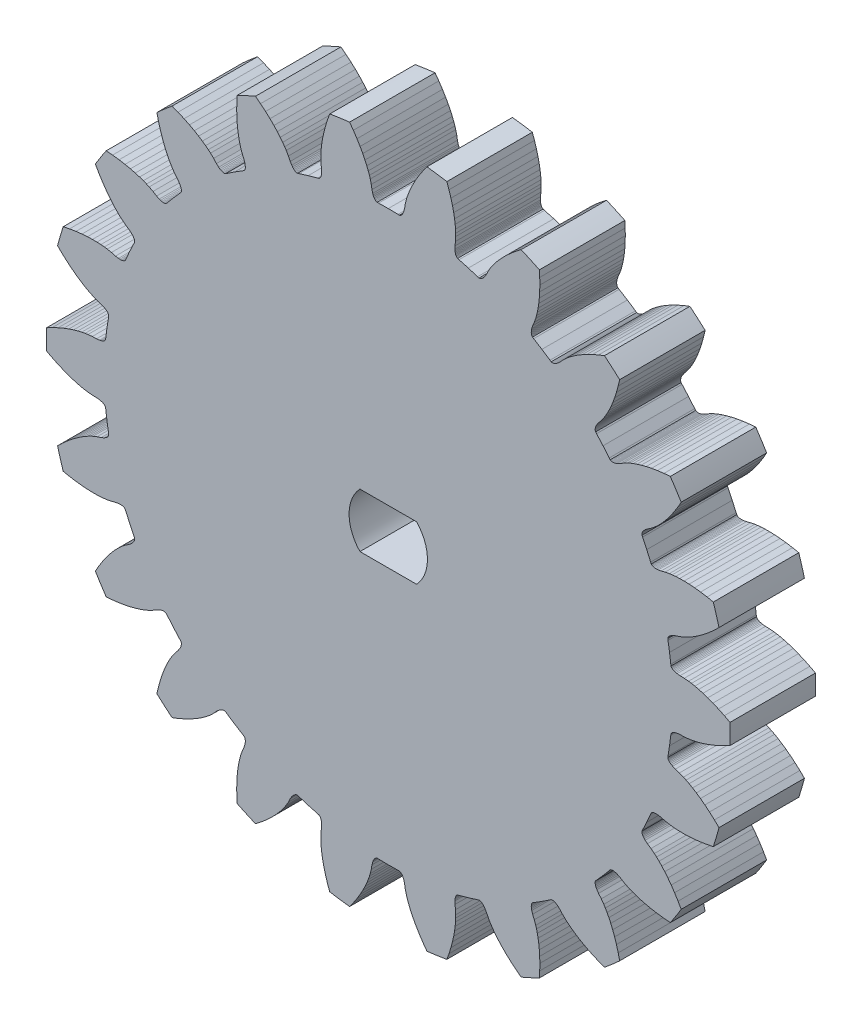
SolidWorks part; units mm, degrees
ref_plane "Front Plane" through (0, 0, 0) normal (0, 0, 1) x (1, 0, 0)
ref_plane "Top Plane" through (0, 0, 0) normal (0, 1, 0) x (1, 0, 0)
ref_plane "Right Plane" through (0, 0, 0) normal (1, 0, 0) x (0, 0, -1)
sketch "Model" plane through (0, 0, 0) normal (0, 0, 1) x (1, 0, 0)
  line L0 (22.8954, 5.7696) -> (22.552, 5.462)
  line L1 (22.552, 5.462) -> (22.2263, 5.1941)
  line L2 (22.2263, 5.1941) -> (21.9171, 4.9606)
  line L3 (21.9171, 4.9606) -> (21.6288, 4.7614)
  line L4 (21.6288, 4.7614) -> (21.3631, 4.5937)
  line L5 (21.3631, 4.5937) -> (21.1212, 4.4548)
  line L6 (21.1212, 4.4548) -> (20.9056, 4.3428)
  line L7 (20.9056, 4.3428) -> (20.7215, 4.2567)
  line L8 (20.7215, 4.2567) -> (20.4399, 4.145)
  line L9 (20.4399, 4.145) -> (20.1563, 4.0551)
  line L10 (20.1563, 4.0551) -> (19.9653, 3.974)
  line L11 (19.9653, 3.974) -> (19.8856, 3.9306)
  line L12 (19.8856, 3.9306) -> (19.8164, 3.8857)
  line L13 (19.8164, 3.8857) -> (19.7579, 3.8399)
  line L14 (19.7579, 3.8399) -> (19.7099, 3.7936)
  line L15 (19.7099, 3.7936) -> (19.6726, 3.7471)
  line L16 (19.6726, 3.7471) -> (19.6458, 3.7009)
  line L17 (19.6458, 3.7009) -> (19.6296, 3.6554)
  line L18 (19.6296, 3.6554) -> (19.6238, 3.6111)
  line L19 (19.6238, 3.6111) -> (19.6389, 3.5098)
  line L20 (19.6389, 3.5098) -> (19.7469, 2.8392)
  line L21 (19.7469, 2.8392) -> (19.8322, 2.1653)
  line L22 (19.8322, 2.1653) -> (19.8463, 2.0638)
  line L23 (19.8463, 2.0638) -> (19.8643, 2.0229)
  line L24 (19.8643, 2.0229) -> (19.8927, 1.9839)
  line L25 (19.8927, 1.9839) -> (19.9314, 1.9471)
  line L26 (19.9314, 1.9471) -> (19.9803, 1.913)
  line L27 (19.9803, 1.913) -> (20.0394, 1.8821)
  line L28 (20.0394, 1.8821) -> (20.1085, 1.8546)
  line L29 (20.1085, 1.8546) -> (20.1874, 1.831)
  line L30 (20.1874, 1.831) -> (20.2762, 1.8118)
  line L31 (20.2762, 1.8118) -> (20.4822, 1.7879)
  line L32 (20.4822, 1.7879) -> (20.7797, 1.7815)
  line L33 (20.7797, 1.7815) -> (21.0814, 1.7537)
  line L34 (21.0814, 1.7537) -> (21.2823, 1.7229)
  line L35 (21.2823, 1.7229) -> (21.5207, 1.6762)
  line L36 (21.5207, 1.6762) -> (21.7919, 1.6111)
  line L37 (21.7919, 1.6111) -> (22.0942, 1.525)
  line L38 (22.0942, 1.525) -> (22.4268, 1.4151)
  line L39 (22.4268, 1.4151) -> (22.7893, 1.2782)
  line L40 (22.7893, 1.2782) -> (23.1773, 1.1129)
  line L41 (23.1773, 1.1129) -> (23.5935, 0.9145)
  line L42 (23.5935, 0.9145) -> (23.9896, 0.7057)
  line L43 (23.9896, -0.7057) -> (23.5935, -0.9145)
  line L44 (23.5935, -0.9145) -> (23.1773, -1.1129)
  line L45 (23.1773, -1.1129) -> (22.7893, -1.2782)
  line L46 (22.7893, -1.2782) -> (22.4268, -1.4151)
  line L47 (22.4268, -1.4151) -> (22.0942, -1.525)
  line L48 (22.0942, -1.525) -> (21.7919, -1.6111)
  line L49 (21.7919, -1.6111) -> (21.5207, -1.6762)
  line L50 (21.5207, -1.6762) -> (21.2823, -1.7229)
  line L51 (21.2823, -1.7229) -> (21.0814, -1.7537)
  line L52 (21.0814, -1.7537) -> (20.7797, -1.7815)
  line L53 (20.7797, -1.7815) -> (20.4822, -1.7879)
  line L54 (20.4822, -1.7879) -> (20.2762, -1.8118)
  line L55 (20.2762, -1.8118) -> (20.1874, -1.831)
  line L56 (20.1874, -1.831) -> (20.1085, -1.8546)
  line L57 (20.1085, -1.8546) -> (20.0394, -1.8821)
  line L58 (20.0394, -1.8821) -> (19.9803, -1.913)
  line L59 (19.9803, -1.913) -> (19.9314, -1.9471)
  line L60 (19.9314, -1.9471) -> (19.8927, -1.9839)
  line L61 (19.8927, -1.9839) -> (19.8643, -2.0229)
  line L62 (19.8643, -2.0229) -> (19.8463, -2.0638)
  line L63 (19.8463, -2.0638) -> (19.8322, -2.1653)
  line L64 (19.8322, -2.1653) -> (19.7469, -2.8392)
  line L65 (19.7469, -2.8392) -> (19.6389, -3.5098)
  line L66 (19.6389, -3.5098) -> (19.6238, -3.6111)
  line L67 (19.6238, -3.6111) -> (19.6296, -3.6554)
  line L68 (19.6296, -3.6554) -> (19.6458, -3.7009)
  line L69 (19.6458, -3.7009) -> (19.6726, -3.7471)
  line L70 (19.6726, -3.7471) -> (19.7099, -3.7936)
  line L71 (19.7099, -3.7936) -> (19.7579, -3.8399)
  line L72 (19.7579, -3.8399) -> (19.8164, -3.8857)
  line L73 (19.8164, -3.8857) -> (19.8856, -3.9306)
  line L74 (19.8856, -3.9306) -> (19.9653, -3.974)
  line L75 (19.9653, -3.974) -> (20.1563, -4.0551)
  line L76 (20.1563, -4.0551) -> (20.4399, -4.145)
  line L77 (20.4399, -4.145) -> (20.7215, -4.2567)
  line L78 (20.7215, -4.2567) -> (20.9056, -4.3428)
  line L79 (20.9056, -4.3428) -> (21.1212, -4.4548)
  line L80 (21.1212, -4.4548) -> (21.3631, -4.5937)
  line L81 (21.3631, -4.5937) -> (21.6288, -4.7614)
  line L82 (21.6288, -4.7614) -> (21.9171, -4.9606)
  line L83 (21.9171, -4.9606) -> (22.2263, -5.1941)
  line L84 (22.2263, -5.1941) -> (22.552, -5.462)
  line L85 (22.552, -5.462) -> (22.8954, -5.7696)
  line L86 (22.8954, -5.7696) -> (23.2167, -6.0816)
  line L87 (22.819, -7.4357) -> (22.3801, -7.5245)
  line L88 (22.3801, -7.5245) -> (21.9249, -7.5976)
  line L89 (21.9249, -7.5976) -> (21.5061, -7.6469)
  line L90 (21.5061, -7.6469) -> (21.1197, -7.6761)
  line L91 (21.1197, -7.6761) -> (20.7695, -7.6879)
  line L92 (20.7695, -7.6879) -> (20.4553, -7.6853)
  line L93 (20.4553, -7.6853) -> (20.1768, -7.6713)
  line L94 (20.1768, -7.6713) -> (19.9348, -7.649)
  line L95 (19.9348, -7.649) -> (19.7334, -7.6219)
  line L96 (19.7334, -7.6219) -> (19.4361, -7.5637)
  line L97 (19.4361, -7.5637) -> (19.1489, -7.486)
  line L98 (19.1489, -7.486) -> (18.9444, -7.4509)
  line L99 (18.9444, -7.4509) -> (18.8538, -7.4443)
  line L100 (18.8538, -7.4443) -> (18.7714, -7.4447)
  line L101 (18.7714, -7.4447) -> (18.6974, -7.4516)
  line L102 (18.6974, -7.4516) -> (18.632, -7.4647)
  line L103 (18.632, -7.4647) -> (18.5755, -7.4836)
  line L104 (18.5755, -7.4836) -> (18.528, -7.5079)
  line L105 (18.528, -7.5079) -> (18.4897, -7.5374)
  line L106 (18.4897, -7.5374) -> (18.4609, -7.5716)
  line L107 (18.4609, -7.5716) -> (18.4188, -7.665)
  line L108 (18.4188, -7.665) -> (18.1472, -8.2875)
  line L109 (18.1472, -8.2875) -> (17.8546, -8.9005)
  line L110 (17.8546, -8.9005) -> (17.8116, -8.9935)
  line L111 (17.8116, -8.9935) -> (17.8046, -9.0377)
  line L112 (17.8046, -9.0377) -> (17.8074, -9.0859)
  line L113 (17.8074, -9.0859) -> (17.82, -9.1377)
  line L114 (17.82, -9.1377) -> (17.8428, -9.1928)
  line L115 (17.8428, -9.1928) -> (17.8757, -9.2508)
  line L116 (17.8757, -9.2508) -> (17.919, -9.3113)
  line L117 (17.919, -9.3113) -> (17.9727, -9.3738)
  line L118 (17.9727, -9.3738) -> (18.0369, -9.4379)
  line L119 (18.0369, -9.4379) -> (18.1974, -9.5695)
  line L120 (18.1974, -9.5695) -> (18.4442, -9.7357)
  line L121 (18.4442, -9.7357) -> (18.6829, -9.9222)
  line L122 (18.6829, -9.9222) -> (18.8353, -10.0567)
  line L123 (18.8353, -10.0567) -> (19.0106, -10.2249)
  line L124 (19.0106, -10.2249) -> (19.2035, -10.4263)
  line L125 (19.2035, -10.4263) -> (19.4113, -10.6621)
  line L126 (19.4113, -10.6621) -> (19.6317, -10.9344)
  line L127 (19.6317, -10.9344) -> (19.8626, -11.2455)
  line L128 (19.8626, -11.2455) -> (20.0996, -11.5944)
  line L129 (20.0996, -11.5944) -> (20.3425, -11.9863)
  line L130 (20.3425, -11.9863) -> (20.5629, -12.3761)
  line L131 (19.7998, -13.5634) -> (19.3537, -13.525)
  line L132 (19.3537, -13.525) -> (18.8963, -13.4668)
  line L133 (18.8963, -13.4668) -> (18.4805, -13.3961)
  line L134 (18.4805, -13.3961) -> (18.1016, -13.3153)
  line L135 (18.1016, -13.3153) -> (17.7623, -13.2279)
  line L136 (17.7623, -13.2279) -> (17.4615, -13.1369)
  line L137 (17.4615, -13.1369) -> (17.1982, -13.0451)
  line L138 (17.1982, -13.0451) -> (16.9723, -12.9555)
  line L139 (16.9723, -12.9555) -> (16.7867, -12.8727)
  line L140 (16.7867, -12.8727) -> (16.5179, -12.7331)
  line L141 (16.5179, -12.7331) -> (16.2642, -12.5776)
  line L142 (16.2642, -12.5776) -> (16.0778, -12.4863)
  line L143 (16.0778, -12.4863) -> (15.9928, -12.4545)
  line L144 (15.9928, -12.4545) -> (15.9136, -12.4316)
  line L145 (15.9136, -12.4316) -> (15.8407, -12.4174)
  line L146 (15.8407, -12.4174) -> (15.7743, -12.4115)
  line L147 (15.7743, -12.4115) -> (15.7147, -12.4137)
  line L148 (15.7147, -12.4137) -> (15.6622, -12.4237)
  line L149 (15.6622, -12.4237) -> (15.6172, -12.4412)
  line L150 (15.6172, -12.4412) -> (15.58, -12.4659)
  line L151 (15.58, -12.4659) -> (15.5133, -12.5437)
  line L152 (15.5133, -12.5437) -> (15.0772, -13.0645)
  line L153 (15.0772, -13.0645) -> (14.6238, -13.5702)
  line L154 (14.6238, -13.5702) -> (14.5563, -13.6473)
  line L155 (14.5563, -13.6473) -> (14.5372, -13.6877)
  line L156 (14.5372, -13.6877) -> (14.5263, -13.7347)
  line L157 (14.5263, -13.7347) -> (14.5238, -13.7881)
  line L158 (14.5238, -13.7881) -> (14.5301, -13.8473)
  line L159 (14.5301, -13.8473) -> (14.5454, -13.9123)
  line L160 (14.5454, -13.9123) -> (14.5699, -13.9825)
  line L161 (14.5699, -13.9825) -> (14.6038, -14.0576)
  line L162 (14.6038, -14.0576) -> (14.6473, -14.1372)
  line L163 (14.6473, -14.1372) -> (14.7642, -14.3086)
  line L164 (14.7642, -14.3086) -> (14.9542, -14.5376)
  line L165 (14.9542, -14.5376) -> (15.1307, -14.7838)
  line L166 (15.1307, -14.7838) -> (15.239, -14.9558)
  line L167 (15.239, -14.9558) -> (15.3598, -15.1666)
  line L168 (15.3598, -15.1666) -> (15.4882, -15.4142)
  line L169 (15.4882, -15.4142) -> (15.6211, -15.699)
  line L170 (15.6211, -15.699) -> (15.7559, -16.0224)
  line L171 (15.7559, -16.0224) -> (15.8898, -16.386)
  line L172 (15.8898, -16.386) -> (16.0189, -16.7874)
  line L173 (16.0189, -16.7874) -> (16.1416, -17.2319)
  line L174 (16.1416, -17.2319) -> (16.2432, -17.668)
  line L175 (15.1765, -18.5922) -> (14.7593, -18.4297)
  line L176 (14.7593, -18.4297) -> (14.3368, -18.245)
  line L177 (14.3368, -18.245) -> (13.9578, -18.06)
  line L178 (13.9578, -18.06) -> (13.617, -17.8757)
  line L179 (13.617, -17.8757) -> (13.3161, -17.6963)
  line L180 (13.3161, -17.6963) -> (13.0531, -17.5242)
  line L181 (13.0531, -17.5242) -> (12.8263, -17.3619)
  line L182 (12.8263, -17.3619) -> (12.6348, -17.2123)
  line L183 (12.6348, -17.2123) -> (12.48, -17.0806)
  line L184 (12.48, -17.0806) -> (12.2614, -16.8709)
  line L185 (12.2614, -16.8709) -> (12.0618, -16.6503)
  line L186 (12.0618, -16.6503) -> (11.9088, -16.5102)
  line L187 (11.9088, -16.5102) -> (11.8361, -16.4557)
  line L188 (11.8361, -16.4557) -> (11.7666, -16.4115)
  line L189 (11.7666, -16.4115) -> (11.7006, -16.3772)
  line L190 (11.7006, -16.3772) -> (11.6386, -16.3529)
  line L191 (11.6386, -16.3529) -> (11.5808, -16.3382)
  line L192 (11.5808, -16.3382) -> (11.5276, -16.3331)
  line L193 (11.5276, -16.3331) -> (11.4795, -16.3372)
  line L194 (11.4795, -16.3372) -> (11.4368, -16.3503)
  line L195 (11.4368, -16.3503) -> (11.3509, -16.4062)
  line L196 (11.3509, -16.4062) -> (10.7858, -16.783)
  line L197 (10.7858, -16.783) -> (10.2082, -17.1405)
  line L198 (10.2082, -17.1405) -> (10.1218, -17.1955)
  line L199 (10.1218, -17.1955) -> (10.092, -17.2289)
  line L200 (10.092, -17.2289) -> (10.0683, -17.2709)
  line L201 (10.0683, -17.2709) -> (10.051, -17.3214)
  line L202 (10.051, -17.3214) -> (10.0403, -17.38)
  line L203 (10.0403, -17.38) -> (10.0366, -17.4466)
  line L204 (10.0366, -17.4466) -> (10.0404, -17.5209)
  line L205 (10.0404, -17.5209) -> (10.0517, -17.6025)
  line L206 (10.0517, -17.6025) -> (10.0711, -17.6912)
  line L207 (10.0711, -17.6912) -> (10.135, -17.8886)
  line L208 (10.135, -17.8886) -> (10.2527, -18.1618)
  line L209 (10.2527, -18.1618) -> (10.3527, -18.4478)
  line L210 (10.3527, -18.4478) -> (10.4082, -18.6433)
  line L211 (10.4082, -18.6433) -> (10.4647, -18.8797)
  line L212 (10.4647, -18.8797) -> (10.5182, -19.1533)
  line L213 (10.5182, -19.1533) -> (10.5654, -19.464)
  line L214 (10.5654, -19.464) -> (10.6036, -19.8123)
  line L215 (10.6036, -19.8123) -> (10.6297, -20.1989)
  line L216 (10.6297, -20.1989) -> (10.6405, -20.6205)
  line L217 (10.6405, -20.6205) -> (10.633, -21.0815)
  line L218 (10.633, -21.0815) -> (10.6075, -21.5286)
  line L219 (9.3237, -22.1149) -> (8.9692, -21.8413)
  line L220 (8.9692, -21.8413) -> (8.6159, -21.5451)
  line L221 (8.6159, -21.5451) -> (8.3043, -21.2609)
  line L222 (8.3043, -21.2609) -> (8.0293, -20.988)
  line L223 (8.0293, -20.988) -> (7.791, -20.7311)
  line L224 (7.791, -20.7311) -> (7.5872, -20.4919)
  line L225 (7.5872, -20.4919) -> (7.4154, -20.2723)
  line L226 (7.4154, -20.2723) -> (7.2738, -20.0748)
  line L227 (7.2738, -20.0748) -> (7.1623, -19.9048)
  line L228 (7.1623, -19.9048) -> (7.0117, -19.642)
  line L229 (7.0117, -19.642) -> (6.8823, -19.374)
  line L230 (6.8823, -19.374) -> (6.7749, -19.1965)
  line L231 (6.7749, -19.1965) -> (6.7206, -19.1238)
  line L232 (6.7206, -19.1238) -> (6.6664, -19.0617)
  line L233 (6.6664, -19.0617) -> (6.6127, -19.0103)
  line L234 (6.6127, -19.0103) -> (6.56, -18.9694)
  line L235 (6.56, -18.9694) -> (6.5086, -18.9391)
  line L236 (6.5086, -18.9391) -> (6.4591, -18.9192)
  line L237 (6.4591, -18.9192) -> (6.4118, -18.9096)
  line L238 (6.4118, -18.9096) -> (6.3671, -18.9102)
  line L239 (6.3671, -18.9102) -> (6.269, -18.9395)
  line L240 (6.269, -18.9395) -> (5.6206, -19.1419)
  line L241 (5.6206, -19.1419) -> (4.9657, -19.3222)
  line L242 (4.9657, -19.3222) -> (4.8672, -19.3506)
  line L243 (4.8672, -19.3506) -> (4.8293, -19.3742)
  line L244 (4.8293, -19.3742) -> (4.7947, -19.4079)
  line L245 (4.7947, -19.4079) -> (4.7638, -19.4514)
  line L246 (4.7638, -19.4514) -> (4.7371, -19.5047)
  line L247 (4.7371, -19.5047) -> (4.7148, -19.5676)
  line L248 (4.7148, -19.5676) -> (4.6975, -19.6399)
  line L249 (4.6975, -19.6399) -> (4.6854, -19.7214)
  line L250 (4.6854, -19.7214) -> (4.679, -19.8119)
  line L251 (4.679, -19.8119) -> (4.6846, -20.0193)
  line L252 (4.6846, -20.0193) -> (4.7206, -20.3147)
  line L253 (4.7206, -20.3147) -> (4.736, -20.6172)
  line L254 (4.736, -20.6172) -> (4.7341, -20.8205)
  line L255 (4.7341, -20.8205) -> (4.7218, -21.0631)
  line L256 (4.7218, -21.0631) -> (4.696, -21.3408)
  line L257 (4.696, -21.3408) -> (4.6538, -21.6522)
  line L258 (4.6538, -21.6522) -> (4.5923, -21.9972)
  line L259 (4.5923, -21.9972) -> (4.5084, -22.3754)
  line L260 (4.5084, -22.3754) -> (4.4, -22.783)
  line L261 (4.4, -22.783) -> (4.2629, -23.2232)
  line L262 (4.2629, -23.2232) -> (4.1126, -23.645)
  line L263 (2.7156, -23.8458) -> (2.4525, -23.4835)
  line L264 (2.4525, -23.4835) -> (2.1969, -23.0997)
  line L265 (2.1969, -23.0997) -> (1.9781, -22.7392)
  line L266 (1.9781, -22.7392) -> (1.791, -22.4)
  line L267 (1.791, -22.4) -> (1.6348, -22.0863)
  line L268 (1.6348, -22.0863) -> (1.5066, -21.7994)
  line L269 (1.5066, -21.7994) -> (1.4036, -21.5402)
  line L270 (1.4036, -21.5402) -> (1.3234, -21.3108)
  line L271 (1.3234, -21.3108) -> (1.2644, -21.1164)
  line L272 (1.2644, -21.1164) -> (1.1939, -20.8218)
  line L273 (1.1939, -20.8218) -> (1.1452, -20.5282)
  line L274 (1.1452, -20.5282) -> (1.0922, -20.3276)
  line L275 (1.0922, -20.3276) -> (1.0606, -20.2425)
  line L276 (1.0606, -20.2425) -> (1.026, -20.1677)
  line L277 (1.026, -20.1677) -> (0.989, -20.1033)
  line L278 (0.989, -20.1033) -> (0.9499, -20.0492)
  line L279 (0.9499, -20.0492) -> (0.9092, -20.0056)
  line L280 (0.9092, -20.0056) -> (0.8673, -19.9725)
  line L281 (0.8673, -19.9725) -> (0.8247, -19.95)
  line L282 (0.8247, -19.95) -> (0.7816, -19.938)
  line L283 (0.7816, -19.938) -> (0.6792, -19.9385)
  line L284 (0.6792, -19.9385) -> (0, -19.95)
  line L285 (0, -19.95) -> (-0.6792, -19.9385)
  line L286 (-0.6792, -19.9385) -> (-0.7816, -19.938)
  line L287 (-0.7816, -19.938) -> (-0.8247, -19.95)
  line L288 (-0.8247, -19.95) -> (-0.8673, -19.9725)
  line L289 (-0.8673, -19.9725) -> (-0.9092, -20.0056)
  line L290 (-0.9092, -20.0056) -> (-0.9499, -20.0492)
  line L291 (-0.9499, -20.0492) -> (-0.989, -20.1033)
  line L292 (-0.989, -20.1033) -> (-1.026, -20.1677)
  line L293 (-1.026, -20.1677) -> (-1.0606, -20.2425)
  line L294 (-1.0606, -20.2425) -> (-1.0922, -20.3276)
  line L295 (-1.0922, -20.3276) -> (-1.1452, -20.5282)
  line L296 (-1.1452, -20.5282) -> (-1.1939, -20.8218)
  line L297 (-1.1939, -20.8218) -> (-1.2644, -21.1164)
  line L298 (-1.2644, -21.1164) -> (-1.3234, -21.3108)
  line L299 (-1.3234, -21.3108) -> (-1.4036, -21.5402)
  line L300 (-1.4036, -21.5402) -> (-1.5066, -21.7994)
  line L301 (-1.5066, -21.7994) -> (-1.6348, -22.0863)
  line L302 (-1.6348, -22.0863) -> (-1.791, -22.4)
  line L303 (-1.791, -22.4) -> (-1.9781, -22.7392)
  line L304 (-1.9781, -22.7392) -> (-2.1969, -23.0997)
  line L305 (-2.1969, -23.0997) -> (-2.4525, -23.4835)
  line L306 (-2.4525, -23.4835) -> (-2.7156, -23.8458)
  line L307 (-4.1126, -23.645) -> (-4.2629, -23.2232)
  line L308 (-4.2629, -23.2232) -> (-4.4, -22.783)
  line L309 (-4.4, -22.783) -> (-4.5084, -22.3754)
  line L310 (-4.5084, -22.3754) -> (-4.5923, -21.9972)
  line L311 (-4.5923, -21.9972) -> (-4.6538, -21.6522)
  line L312 (-4.6538, -21.6522) -> (-4.696, -21.3408)
  line L313 (-4.696, -21.3408) -> (-4.7218, -21.0631)
  line L314 (-4.7218, -21.0631) -> (-4.7341, -20.8205)
  line L315 (-4.7341, -20.8205) -> (-4.736, -20.6172)
  line L316 (-4.736, -20.6172) -> (-4.7206, -20.3147)
  line L317 (-4.7206, -20.3147) -> (-4.6846, -20.0193)
  line L318 (-4.6846, -20.0193) -> (-4.679, -19.8119)
  line L319 (-4.679, -19.8119) -> (-4.6854, -19.7214)
  line L320 (-4.6854, -19.7214) -> (-4.6975, -19.6399)
  line L321 (-4.6975, -19.6399) -> (-4.7148, -19.5676)
  line L322 (-4.7148, -19.5676) -> (-4.7371, -19.5047)
  line L323 (-4.7371, -19.5047) -> (-4.7638, -19.4514)
  line L324 (-4.7638, -19.4514) -> (-4.7947, -19.4079)
  line L325 (-4.7947, -19.4079) -> (-4.8293, -19.3742)
  line L326 (-4.8293, -19.3742) -> (-4.8672, -19.3506)
  line L327 (-4.8672, -19.3506) -> (-4.9657, -19.3222)
  line L328 (-4.9657, -19.3222) -> (-5.6206, -19.1419)
  line L329 (-5.6206, -19.1419) -> (-6.269, -18.9395)
  line L330 (-6.269, -18.9395) -> (-6.3671, -18.9102)
  line L331 (-6.3671, -18.9102) -> (-6.4118, -18.9096)
  line L332 (-6.4118, -18.9096) -> (-6.4591, -18.9192)
  line L333 (-6.4591, -18.9192) -> (-6.5086, -18.9391)
  line L334 (-6.5086, -18.9391) -> (-6.56, -18.9694)
  line L335 (-6.56, -18.9694) -> (-6.6127, -19.0103)
  line L336 (-6.6127, -19.0103) -> (-6.6664, -19.0617)
  line L337 (-6.6664, -19.0617) -> (-6.7206, -19.1238)
  line L338 (-6.7206, -19.1238) -> (-6.7749, -19.1965)
  line L339 (-6.7749, -19.1965) -> (-6.8823, -19.374)
  line L340 (-6.8823, -19.374) -> (-7.0117, -19.642)
  line L341 (-7.0117, -19.642) -> (-7.1623, -19.9048)
  line L342 (-7.1623, -19.9048) -> (-7.2738, -20.0748)
  line L343 (-7.2738, -20.0748) -> (-7.4154, -20.2723)
  line L344 (-7.4154, -20.2723) -> (-7.5872, -20.4919)
  line L345 (-7.5872, -20.4919) -> (-7.791, -20.7311)
  line L346 (-7.791, -20.7311) -> (-8.0293, -20.988)
  line L347 (-8.0293, -20.988) -> (-8.3043, -21.2609)
  line L348 (-8.3043, -21.2609) -> (-8.6159, -21.5451)
  line L349 (-8.6159, -21.5451) -> (-8.9692, -21.8413)
  line L350 (-8.9692, -21.8413) -> (-9.3237, -22.1149)
  line L351 (-10.6075, -21.5286) -> (-10.633, -21.0815)
  line L352 (-10.633, -21.0815) -> (-10.6405, -20.6205)
  line L353 (-10.6405, -20.6205) -> (-10.6297, -20.1989)
  line L354 (-10.6297, -20.1989) -> (-10.6036, -19.8123)
  line L355 (-10.6036, -19.8123) -> (-10.5654, -19.464)
  line L356 (-10.5654, -19.464) -> (-10.5182, -19.1533)
  line L357 (-10.5182, -19.1533) -> (-10.4647, -18.8797)
  line L358 (-10.4647, -18.8797) -> (-10.4082, -18.6433)
  line L359 (-10.4082, -18.6433) -> (-10.3527, -18.4478)
  line L360 (-10.3527, -18.4478) -> (-10.2527, -18.1618)
  line L361 (-10.2527, -18.1618) -> (-10.135, -17.8886)
  line L362 (-10.135, -17.8886) -> (-10.0711, -17.6912)
  line L363 (-10.0711, -17.6912) -> (-10.0517, -17.6025)
  line L364 (-10.0517, -17.6025) -> (-10.0404, -17.5209)
  line L365 (-10.0404, -17.5209) -> (-10.0366, -17.4466)
  line L366 (-10.0366, -17.4466) -> (-10.0403, -17.38)
  line L367 (-10.0403, -17.38) -> (-10.051, -17.3214)
  line L368 (-10.051, -17.3214) -> (-10.0683, -17.2709)
  line L369 (-10.0683, -17.2709) -> (-10.092, -17.2289)
  line L370 (-10.092, -17.2289) -> (-10.1218, -17.1955)
  line L371 (-10.1218, -17.1955) -> (-10.2082, -17.1405)
  line L372 (-10.2082, -17.1405) -> (-10.7858, -16.783)
  line L373 (-10.7858, -16.783) -> (-11.3509, -16.4062)
  line L374 (-11.3509, -16.4062) -> (-11.4368, -16.3503)
  line L375 (-11.4368, -16.3503) -> (-11.4795, -16.3372)
  line L376 (-11.4795, -16.3372) -> (-11.5276, -16.3331)
  line L377 (-11.5276, -16.3331) -> (-11.5808, -16.3382)
  line L378 (-11.5808, -16.3382) -> (-11.6386, -16.3529)
  line L379 (-11.6386, -16.3529) -> (-11.7006, -16.3772)
  line L380 (-11.7006, -16.3772) -> (-11.7666, -16.4115)
  line L381 (-11.7666, -16.4115) -> (-11.8361, -16.4557)
  line L382 (-11.8361, -16.4557) -> (-11.9088, -16.5102)
  line L383 (-11.9088, -16.5102) -> (-12.0618, -16.6503)
  line L384 (-12.0618, -16.6503) -> (-12.2614, -16.8709)
  line L385 (-12.2614, -16.8709) -> (-12.48, -17.0806)
  line L386 (-12.48, -17.0806) -> (-12.6348, -17.2123)
  line L387 (-12.6348, -17.2123) -> (-12.8263, -17.3619)
  line L388 (-12.8263, -17.3619) -> (-13.0531, -17.5242)
  line L389 (-13.0531, -17.5242) -> (-13.3161, -17.6963)
  line L390 (-13.3161, -17.6963) -> (-13.617, -17.8757)
  line L391 (-13.617, -17.8757) -> (-13.9578, -18.06)
  line L392 (-13.9578, -18.06) -> (-14.3368, -18.245)
  line L393 (-14.3368, -18.245) -> (-14.7593, -18.4297)
  line L394 (-14.7593, -18.4297) -> (-15.1765, -18.5922)
  line L395 (-16.2432, -17.668) -> (-16.1416, -17.2319)
  line L396 (-16.1416, -17.2319) -> (-16.0189, -16.7874)
  line L397 (-16.0189, -16.7874) -> (-15.8898, -16.386)
  line L398 (-15.8898, -16.386) -> (-15.7559, -16.0224)
  line L399 (-15.7559, -16.0224) -> (-15.6211, -15.699)
  line L400 (-15.6211, -15.699) -> (-15.4882, -15.4142)
  line L401 (-15.4882, -15.4142) -> (-15.3598, -15.1666)
  line L402 (-15.3598, -15.1666) -> (-15.239, -14.9558)
  line L403 (-15.239, -14.9558) -> (-15.1307, -14.7838)
  line L404 (-15.1307, -14.7838) -> (-14.9542, -14.5376)
  line L405 (-14.9542, -14.5376) -> (-14.7642, -14.3086)
  line L406 (-14.7642, -14.3086) -> (-14.6473, -14.1372)
  line L407 (-14.6473, -14.1372) -> (-14.6038, -14.0576)
  line L408 (-14.6038, -14.0576) -> (-14.5699, -13.9825)
  line L409 (-14.5699, -13.9825) -> (-14.5454, -13.9123)
  line L410 (-14.5454, -13.9123) -> (-14.5301, -13.8473)
  line L411 (-14.5301, -13.8473) -> (-14.5238, -13.7881)
  line L412 (-14.5238, -13.7881) -> (-14.5263, -13.7347)
  line L413 (-14.5263, -13.7347) -> (-14.5372, -13.6877)
  line L414 (-14.5372, -13.6877) -> (-14.5563, -13.6473)
  line L415 (-14.5563, -13.6473) -> (-14.6238, -13.5702)
  line L416 (-14.6238, -13.5702) -> (-15.0772, -13.0645)
  line L417 (-15.0772, -13.0645) -> (-15.5133, -12.5437)
  line L418 (-15.5133, -12.5437) -> (-15.58, -12.4659)
  line L419 (-15.58, -12.4659) -> (-15.6172, -12.4412)
  line L420 (-15.6172, -12.4412) -> (-15.6622, -12.4237)
  line L421 (-15.6622, -12.4237) -> (-15.7147, -12.4137)
  line L422 (-15.7147, -12.4137) -> (-15.7743, -12.4115)
  line L423 (-15.7743, -12.4115) -> (-15.8407, -12.4174)
  line L424 (-15.8407, -12.4174) -> (-15.9136, -12.4316)
  line L425 (-15.9136, -12.4316) -> (-15.9928, -12.4545)
  line L426 (-15.9928, -12.4545) -> (-16.0778, -12.4863)
  line L427 (-16.0778, -12.4863) -> (-16.2642, -12.5776)
  line L428 (-16.2642, -12.5776) -> (-16.5179, -12.7331)
  line L429 (-16.5179, -12.7331) -> (-16.7867, -12.8727)
  line L430 (-16.7867, -12.8727) -> (-16.9723, -12.9555)
  line L431 (-16.9723, -12.9555) -> (-17.1982, -13.0451)
  line L432 (-17.1982, -13.0451) -> (-17.4615, -13.1369)
  line L433 (-17.4615, -13.1369) -> (-17.7623, -13.2279)
  line L434 (-17.7623, -13.2279) -> (-18.1016, -13.3153)
  line L435 (-18.1016, -13.3153) -> (-18.4805, -13.3961)
  line L436 (-18.4805, -13.3961) -> (-18.8963, -13.4668)
  line L437 (-18.8963, -13.4668) -> (-19.3537, -13.525)
  line L438 (-19.3537, -13.525) -> (-19.7998, -13.5634)
  line L439 (-20.5629, -12.3761) -> (-20.3425, -11.9863)
  line L440 (-20.3425, -11.9863) -> (-20.0996, -11.5944)
  line L441 (-20.0996, -11.5944) -> (-19.8626, -11.2455)
  line L442 (-19.8626, -11.2455) -> (-19.6317, -10.9344)
  line L443 (-19.6317, -10.9344) -> (-19.4113, -10.6621)
  line L444 (-19.4113, -10.6621) -> (-19.2035, -10.4263)
  line L445 (-19.2035, -10.4263) -> (-19.0106, -10.2249)
  line L446 (-19.0106, -10.2249) -> (-18.8353, -10.0567)
  line L447 (-18.8353, -10.0567) -> (-18.6829, -9.9222)
  line L448 (-18.6829, -9.9222) -> (-18.4442, -9.7357)
  line L449 (-18.4442, -9.7357) -> (-18.1974, -9.5695)
  line L450 (-18.1974, -9.5695) -> (-18.0369, -9.4379)
  line L451 (-18.0369, -9.4379) -> (-17.9727, -9.3738)
  line L452 (-17.9727, -9.3738) -> (-17.919, -9.3113)
  line L453 (-17.919, -9.3113) -> (-17.8757, -9.2508)
  line L454 (-17.8757, -9.2508) -> (-17.8428, -9.1928)
  line L455 (-17.8428, -9.1928) -> (-17.82, -9.1377)
  line L456 (-17.82, -9.1377) -> (-17.8074, -9.0859)
  line L457 (-17.8074, -9.0859) -> (-17.8046, -9.0377)
  line L458 (-17.8046, -9.0377) -> (-17.8116, -8.9935)
  line L459 (-17.8116, -8.9935) -> (-17.8546, -8.9005)
  line L460 (-17.8546, -8.9005) -> (-18.1472, -8.2875)
  line L461 (-18.1472, -8.2875) -> (-18.4188, -7.665)
  line L462 (-18.4188, -7.665) -> (-18.4609, -7.5716)
  line L463 (-18.4609, -7.5716) -> (-18.4897, -7.5374)
  line L464 (-18.4897, -7.5374) -> (-18.528, -7.5079)
  line L465 (-18.528, -7.5079) -> (-18.5755, -7.4836)
  line L466 (-18.5755, -7.4836) -> (-18.632, -7.4647)
  line L467 (-18.632, -7.4647) -> (-18.6974, -7.4516)
  line L468 (-18.6974, -7.4516) -> (-18.7714, -7.4447)
  line L469 (-18.7714, -7.4447) -> (-18.8538, -7.4443)
  line L470 (-18.8538, -7.4443) -> (-18.9444, -7.4509)
  line L471 (-18.9444, -7.4509) -> (-19.1489, -7.486)
  line L472 (-19.1489, -7.486) -> (-19.4361, -7.5637)
  line L473 (-19.4361, -7.5637) -> (-19.7334, -7.6219)
  line L474 (-19.7334, -7.6219) -> (-19.9348, -7.649)
  line L475 (-19.9348, -7.649) -> (-20.1768, -7.6713)
  line L476 (-20.1768, -7.6713) -> (-20.4553, -7.6853)
  line L477 (-20.4553, -7.6853) -> (-20.7695, -7.6879)
  line L478 (-20.7695, -7.6879) -> (-21.1197, -7.6761)
  line L479 (-21.1197, -7.6761) -> (-21.5061, -7.6469)
  line L480 (-21.5061, -7.6469) -> (-21.9249, -7.5976)
  line L481 (-21.9249, -7.5976) -> (-22.3801, -7.5245)
  line L482 (-22.3801, -7.5245) -> (-22.819, -7.4357)
  line L483 (-23.2167, -6.0816) -> (-22.8954, -5.7696)
  line L484 (-22.8954, -5.7696) -> (-22.552, -5.462)
  line L485 (-22.552, -5.462) -> (-22.2263, -5.1941)
  line L486 (-22.2263, -5.1941) -> (-21.9171, -4.9606)
  line L487 (-21.9171, -4.9606) -> (-21.6288, -4.7614)
  line L488 (-21.6288, -4.7614) -> (-21.3631, -4.5937)
  line L489 (-21.3631, -4.5937) -> (-21.1212, -4.4548)
  line L490 (-21.1212, -4.4548) -> (-20.9056, -4.3428)
  line L491 (-20.9056, -4.3428) -> (-20.7215, -4.2567)
  line L492 (-20.7215, -4.2567) -> (-20.4399, -4.145)
  line L493 (-20.4399, -4.145) -> (-20.1563, -4.0551)
  line L494 (-20.1563, -4.0551) -> (-19.9653, -3.974)
  line L495 (-19.9653, -3.974) -> (-19.8856, -3.9306)
  line L496 (-19.8856, -3.9306) -> (-19.8164, -3.8857)
  line L497 (-19.8164, -3.8857) -> (-19.7579, -3.8399)
  line L498 (-19.7579, -3.8399) -> (-19.7099, -3.7936)
  line L499 (-19.7099, -3.7936) -> (-19.6726, -3.7471)
  line L500 (-19.6726, -3.7471) -> (-19.6458, -3.7009)
  line L501 (-19.6458, -3.7009) -> (-19.6296, -3.6554)
  line L502 (-19.6296, -3.6554) -> (-19.6238, -3.6111)
  line L503 (-19.6238, -3.6111) -> (-19.6389, -3.5098)
  line L504 (-19.6389, -3.5098) -> (-19.7469, -2.8392)
  line L505 (-19.7469, -2.8392) -> (-19.8322, -2.1653)
  line L506 (-19.8322, -2.1653) -> (-19.8463, -2.0638)
  line L507 (-19.8463, -2.0638) -> (-19.8643, -2.0229)
  line L508 (-19.8643, -2.0229) -> (-19.8927, -1.9839)
  line L509 (-19.8927, -1.9839) -> (-19.9314, -1.9471)
  line L510 (-19.9314, -1.9471) -> (-19.9803, -1.913)
  line L511 (-19.9803, -1.913) -> (-20.0394, -1.8821)
  line L512 (-20.0394, -1.8821) -> (-20.1085, -1.8546)
  line L513 (-20.1085, -1.8546) -> (-20.1874, -1.831)
  line L514 (-20.1874, -1.831) -> (-20.2762, -1.8118)
  line L515 (-20.2762, -1.8118) -> (-20.4822, -1.7879)
  line L516 (-20.4822, -1.7879) -> (-20.7797, -1.7815)
  line L517 (-20.7797, -1.7815) -> (-21.0814, -1.7537)
  line L518 (-21.0814, -1.7537) -> (-21.2823, -1.7229)
  line L519 (-21.2823, -1.7229) -> (-21.5207, -1.6762)
  line L520 (-21.5207, -1.6762) -> (-21.7919, -1.6111)
  line L521 (-21.7919, -1.6111) -> (-22.0942, -1.525)
  line L522 (-22.0942, -1.525) -> (-22.4268, -1.4151)
  line L523 (-22.4268, -1.4151) -> (-22.7893, -1.2782)
  line L524 (-22.7893, -1.2782) -> (-23.1773, -1.1129)
  line L525 (-23.1773, -1.1129) -> (-23.5935, -0.9145)
  line L526 (-23.5935, -0.9145) -> (-23.9896, -0.7057)
  line L527 (-23.9896, 0.7057) -> (-23.5935, 0.9145)
  line L528 (-23.5935, 0.9145) -> (-23.1773, 1.1129)
  line L529 (-23.1773, 1.1129) -> (-22.7893, 1.2782)
  line L530 (-22.7893, 1.2782) -> (-22.4268, 1.4151)
  line L531 (-22.4268, 1.4151) -> (-22.0942, 1.525)
  line L532 (-22.0942, 1.525) -> (-21.7919, 1.6111)
  line L533 (-21.7919, 1.6111) -> (-21.5207, 1.6762)
  line L534 (-21.5207, 1.6762) -> (-21.2823, 1.7229)
  line L535 (-21.2823, 1.7229) -> (-21.0814, 1.7537)
  line L536 (-21.0814, 1.7537) -> (-20.7797, 1.7815)
  line L537 (-20.7797, 1.7815) -> (-20.4822, 1.7879)
  line L538 (-20.4822, 1.7879) -> (-20.2762, 1.8118)
  line L539 (-20.2762, 1.8118) -> (-20.1874, 1.831)
  line L540 (-20.1874, 1.831) -> (-20.1085, 1.8546)
  line L541 (-20.1085, 1.8546) -> (-20.0394, 1.8821)
  line L542 (-20.0394, 1.8821) -> (-19.9803, 1.913)
  line L543 (-19.9803, 1.913) -> (-19.9314, 1.9471)
  line L544 (-19.9314, 1.9471) -> (-19.8927, 1.9839)
  line L545 (-19.8927, 1.9839) -> (-19.8643, 2.0229)
  line L546 (-19.8643, 2.0229) -> (-19.8463, 2.0638)
  line L547 (-19.8463, 2.0638) -> (-19.8322, 2.1653)
  line L548 (-19.8322, 2.1653) -> (-19.7469, 2.8392)
  line L549 (-19.7469, 2.8392) -> (-19.6389, 3.5098)
  line L550 (-19.6389, 3.5098) -> (-19.6238, 3.6111)
  line L551 (-19.6238, 3.6111) -> (-19.6296, 3.6554)
  line L552 (-19.6296, 3.6554) -> (-19.6458, 3.7009)
  line L553 (-19.6458, 3.7009) -> (-19.6726, 3.7471)
  line L554 (-19.6726, 3.7471) -> (-19.7099, 3.7936)
  line L555 (-19.7099, 3.7936) -> (-19.7579, 3.8399)
  line L556 (-19.7579, 3.8399) -> (-19.8164, 3.8857)
  line L557 (-19.8164, 3.8857) -> (-19.8856, 3.9306)
  line L558 (-19.8856, 3.9306) -> (-19.9653, 3.974)
  line L559 (-19.9653, 3.974) -> (-20.1563, 4.0551)
  line L560 (-20.1563, 4.0551) -> (-20.4399, 4.145)
  line L561 (-20.4399, 4.145) -> (-20.7215, 4.2567)
  line L562 (-20.7215, 4.2567) -> (-20.9056, 4.3428)
  line L563 (-20.9056, 4.3428) -> (-21.1212, 4.4548)
  line L564 (-21.1212, 4.4548) -> (-21.3631, 4.5937)
  line L565 (-21.3631, 4.5937) -> (-21.6288, 4.7614)
  line L566 (-21.6288, 4.7614) -> (-21.9171, 4.9606)
  line L567 (-21.9171, 4.9606) -> (-22.2263, 5.1941)
  line L568 (-22.2263, 5.1941) -> (-22.552, 5.462)
  line L569 (-22.552, 5.462) -> (-22.8954, 5.7696)
  line L570 (-22.8954, 5.7696) -> (-23.2167, 6.0816)
  line L571 (-22.819, 7.4357) -> (-22.3801, 7.5245)
  line L572 (-22.3801, 7.5245) -> (-21.9249, 7.5976)
  line L573 (-21.9249, 7.5976) -> (-21.5061, 7.6469)
  line L574 (-21.5061, 7.6469) -> (-21.1197, 7.6761)
  line L575 (-21.1197, 7.6761) -> (-20.7695, 7.6879)
  line L576 (-20.7695, 7.6879) -> (-20.4553, 7.6853)
  line L577 (-20.4553, 7.6853) -> (-20.1768, 7.6713)
  line L578 (-20.1768, 7.6713) -> (-19.9348, 7.649)
  line L579 (-19.9348, 7.649) -> (-19.7334, 7.6219)
  line L580 (-19.7334, 7.6219) -> (-19.4361, 7.5637)
  line L581 (-19.4361, 7.5637) -> (-19.1489, 7.486)
  line L582 (-19.1489, 7.486) -> (-18.9444, 7.4509)
  line L583 (-18.9444, 7.4509) -> (-18.8538, 7.4443)
  line L584 (-18.8538, 7.4443) -> (-18.7714, 7.4447)
  line L585 (-18.7714, 7.4447) -> (-18.6974, 7.4516)
  line L586 (-18.6974, 7.4516) -> (-18.632, 7.4647)
  line L587 (-18.632, 7.4647) -> (-18.5755, 7.4836)
  line L588 (-18.5755, 7.4836) -> (-18.528, 7.5079)
  line L589 (-18.528, 7.5079) -> (-18.4897, 7.5374)
  line L590 (-18.4897, 7.5374) -> (-18.4609, 7.5716)
  line L591 (-18.4609, 7.5716) -> (-18.4188, 7.665)
  line L592 (-18.4188, 7.665) -> (-18.1472, 8.2875)
  line L593 (-18.1472, 8.2875) -> (-17.8546, 8.9005)
  line L594 (-17.8546, 8.9005) -> (-17.8116, 8.9935)
  line L595 (-17.8116, 8.9935) -> (-17.8046, 9.0377)
  line L596 (-17.8046, 9.0377) -> (-17.8074, 9.0859)
  line L597 (-17.8074, 9.0859) -> (-17.82, 9.1377)
  line L598 (-17.82, 9.1377) -> (-17.8428, 9.1928)
  line L599 (-17.8428, 9.1928) -> (-17.8757, 9.2508)
  line L600 (-17.8757, 9.2508) -> (-17.919, 9.3113)
  line L601 (-17.919, 9.3113) -> (-17.9727, 9.3738)
  line L602 (-17.9727, 9.3738) -> (-18.0369, 9.4379)
  line L603 (-18.0369, 9.4379) -> (-18.1974, 9.5695)
  line L604 (-18.1974, 9.5695) -> (-18.4442, 9.7357)
  line L605 (-18.4442, 9.7357) -> (-18.6829, 9.9222)
  line L606 (-18.6829, 9.9222) -> (-18.8353, 10.0567)
  line L607 (-18.8353, 10.0567) -> (-19.0106, 10.2249)
  line L608 (-19.0106, 10.2249) -> (-19.2035, 10.4263)
  line L609 (-19.2035, 10.4263) -> (-19.4113, 10.6621)
  line L610 (-19.4113, 10.6621) -> (-19.6317, 10.9344)
  line L611 (-19.6317, 10.9344) -> (-19.8626, 11.2455)
  line L612 (-19.8626, 11.2455) -> (-20.0996, 11.5944)
  line L613 (-20.0996, 11.5944) -> (-20.3425, 11.9863)
  line L614 (-20.3425, 11.9863) -> (-20.5629, 12.3761)
  line L615 (-19.7998, 13.5634) -> (-19.3537, 13.525)
  line L616 (-19.3537, 13.525) -> (-18.8963, 13.4668)
  line L617 (-18.8963, 13.4668) -> (-18.4805, 13.3961)
  line L618 (-18.4805, 13.3961) -> (-18.1016, 13.3153)
  line L619 (-18.1016, 13.3153) -> (-17.7623, 13.2279)
  line L620 (-17.7623, 13.2279) -> (-17.4615, 13.1369)
  line L621 (-17.4615, 13.1369) -> (-17.1982, 13.0451)
  line L622 (-17.1982, 13.0451) -> (-16.9723, 12.9555)
  line L623 (-16.9723, 12.9555) -> (-16.7867, 12.8727)
  line L624 (-16.7867, 12.8727) -> (-16.5179, 12.7331)
  line L625 (-16.5179, 12.7331) -> (-16.2642, 12.5776)
  line L626 (-16.2642, 12.5776) -> (-16.0778, 12.4863)
  line L627 (-16.0778, 12.4863) -> (-15.9928, 12.4545)
  line L628 (-15.9928, 12.4545) -> (-15.9136, 12.4316)
  line L629 (-15.9136, 12.4316) -> (-15.8407, 12.4174)
  line L630 (-15.8407, 12.4174) -> (-15.7743, 12.4115)
  line L631 (-15.7743, 12.4115) -> (-15.7147, 12.4137)
  line L632 (-15.7147, 12.4137) -> (-15.6622, 12.4237)
  line L633 (-15.6622, 12.4237) -> (-15.6172, 12.4412)
  line L634 (-15.6172, 12.4412) -> (-15.58, 12.4659)
  line L635 (-15.58, 12.4659) -> (-15.5133, 12.5437)
  line L636 (-15.5133, 12.5437) -> (-15.0772, 13.0645)
  line L637 (-15.0772, 13.0645) -> (-14.6238, 13.5702)
  line L638 (-14.6238, 13.5702) -> (-14.5563, 13.6473)
  line L639 (-14.5563, 13.6473) -> (-14.5372, 13.6877)
  line L640 (-14.5372, 13.6877) -> (-14.5263, 13.7347)
  line L641 (-14.5263, 13.7347) -> (-14.5238, 13.7881)
  line L642 (-14.5238, 13.7881) -> (-14.5301, 13.8473)
  line L643 (-14.5301, 13.8473) -> (-14.5454, 13.9123)
  line L644 (-14.5454, 13.9123) -> (-14.5699, 13.9825)
  line L645 (-14.5699, 13.9825) -> (-14.6038, 14.0576)
  line L646 (-14.6038, 14.0576) -> (-14.6473, 14.1372)
  line L647 (-14.6473, 14.1372) -> (-14.7642, 14.3086)
  line L648 (-14.7642, 14.3086) -> (-14.9542, 14.5376)
  line L649 (-14.9542, 14.5376) -> (-15.1307, 14.7838)
  line L650 (-15.1307, 14.7838) -> (-15.239, 14.9558)
  line L651 (-15.239, 14.9558) -> (-15.3598, 15.1666)
  line L652 (-15.3598, 15.1666) -> (-15.4882, 15.4142)
  line L653 (-15.4882, 15.4142) -> (-15.6211, 15.699)
  line L654 (-15.6211, 15.699) -> (-15.7559, 16.0224)
  line L655 (-15.7559, 16.0224) -> (-15.8898, 16.386)
  line L656 (-15.8898, 16.386) -> (-16.0189, 16.7874)
  line L657 (-16.0189, 16.7874) -> (-16.1416, 17.2319)
  line L658 (-16.1416, 17.2319) -> (-16.2432, 17.668)
  line L659 (-15.1765, 18.5922) -> (-14.7593, 18.4297)
  line L660 (-14.7593, 18.4297) -> (-14.3368, 18.245)
  line L661 (-14.3368, 18.245) -> (-13.9578, 18.06)
  line L662 (-13.9578, 18.06) -> (-13.617, 17.8757)
  line L663 (-13.617, 17.8757) -> (-13.3161, 17.6963)
  line L664 (-13.3161, 17.6963) -> (-13.0531, 17.5242)
  line L665 (-13.0531, 17.5242) -> (-12.8263, 17.3619)
  line L666 (-12.8263, 17.3619) -> (-12.6348, 17.2123)
  line L667 (-12.6348, 17.2123) -> (-12.48, 17.0806)
  line L668 (-12.48, 17.0806) -> (-12.2614, 16.8709)
  line L669 (-12.2614, 16.8709) -> (-12.0618, 16.6503)
  line L670 (-12.0618, 16.6503) -> (-11.9088, 16.5102)
  line L671 (-11.9088, 16.5102) -> (-11.8361, 16.4557)
  line L672 (-11.8361, 16.4557) -> (-11.7666, 16.4115)
  line L673 (-11.7666, 16.4115) -> (-11.7006, 16.3772)
  line L674 (-11.7006, 16.3772) -> (-11.6386, 16.3529)
  line L675 (-11.6386, 16.3529) -> (-11.5808, 16.3382)
  line L676 (-11.5808, 16.3382) -> (-11.5276, 16.3331)
  line L677 (-11.5276, 16.3331) -> (-11.4795, 16.3372)
  line L678 (-11.4795, 16.3372) -> (-11.4368, 16.3503)
  line L679 (-11.4368, 16.3503) -> (-11.3509, 16.4062)
  line L680 (-11.3509, 16.4062) -> (-10.7858, 16.783)
  line L681 (-10.7858, 16.783) -> (-10.2082, 17.1405)
  line L682 (-10.2082, 17.1405) -> (-10.1218, 17.1955)
  line L683 (-10.1218, 17.1955) -> (-10.092, 17.2289)
  line L684 (-10.092, 17.2289) -> (-10.0683, 17.2709)
  line L685 (-10.0683, 17.2709) -> (-10.051, 17.3214)
  line L686 (-10.051, 17.3214) -> (-10.0403, 17.38)
  line L687 (-10.0403, 17.38) -> (-10.0366, 17.4466)
  line L688 (-10.0366, 17.4466) -> (-10.0404, 17.5209)
  line L689 (-10.0404, 17.5209) -> (-10.0517, 17.6025)
  line L690 (-10.0517, 17.6025) -> (-10.0711, 17.6912)
  line L691 (-10.0711, 17.6912) -> (-10.135, 17.8886)
  line L692 (-10.135, 17.8886) -> (-10.2527, 18.1618)
  line L693 (-10.2527, 18.1618) -> (-10.3527, 18.4478)
  line L694 (-10.3527, 18.4478) -> (-10.4082, 18.6433)
  line L695 (-10.4082, 18.6433) -> (-10.4647, 18.8797)
  line L696 (-10.4647, 18.8797) -> (-10.5182, 19.1533)
  line L697 (-10.5182, 19.1533) -> (-10.5654, 19.464)
  line L698 (-10.5654, 19.464) -> (-10.6036, 19.8123)
  line L699 (-10.6036, 19.8123) -> (-10.6297, 20.1989)
  line L700 (-10.6297, 20.1989) -> (-10.6405, 20.6205)
  line L701 (-10.6405, 20.6205) -> (-10.633, 21.0815)
  line L702 (-10.633, 21.0815) -> (-10.6075, 21.5286)
  line L703 (-9.3237, 22.1149) -> (-8.9692, 21.8413)
  line L704 (-8.9692, 21.8413) -> (-8.6159, 21.5451)
  line L705 (-8.6159, 21.5451) -> (-8.3043, 21.2609)
  line L706 (-8.3043, 21.2609) -> (-8.0293, 20.988)
  line L707 (-8.0293, 20.988) -> (-7.791, 20.7311)
  line L708 (-7.791, 20.7311) -> (-7.5872, 20.4919)
  line L709 (-7.5872, 20.4919) -> (-7.4154, 20.2723)
  line L710 (-7.4154, 20.2723) -> (-7.2738, 20.0748)
  line L711 (-7.2738, 20.0748) -> (-7.1623, 19.9048)
  line L712 (-7.1623, 19.9048) -> (-7.0117, 19.642)
  line L713 (-7.0117, 19.642) -> (-6.8823, 19.374)
  line L714 (-6.8823, 19.374) -> (-6.7749, 19.1965)
  line L715 (-6.7749, 19.1965) -> (-6.7206, 19.1238)
  line L716 (-6.7206, 19.1238) -> (-6.6664, 19.0617)
  line L717 (-6.6664, 19.0617) -> (-6.6127, 19.0103)
  line L718 (-6.6127, 19.0103) -> (-6.56, 18.9694)
  line L719 (-6.56, 18.9694) -> (-6.5086, 18.9391)
  line L720 (-6.5086, 18.9391) -> (-6.4591, 18.9192)
  line L721 (-6.4591, 18.9192) -> (-6.4118, 18.9096)
  line L722 (-6.4118, 18.9096) -> (-6.3671, 18.9102)
  line L723 (-6.3671, 18.9102) -> (-6.269, 18.9395)
  line L724 (-6.269, 18.9395) -> (-5.6206, 19.1419)
  line L725 (-5.6206, 19.1419) -> (-4.9657, 19.3222)
  line L726 (-4.9657, 19.3222) -> (-4.8672, 19.3506)
  line L727 (-4.8672, 19.3506) -> (-4.8293, 19.3742)
  line L728 (-4.8293, 19.3742) -> (-4.7947, 19.4079)
  line L729 (-4.7947, 19.4079) -> (-4.7638, 19.4514)
  line L730 (-4.7638, 19.4514) -> (-4.7371, 19.5047)
  line L731 (-4.7371, 19.5047) -> (-4.7148, 19.5676)
  line L732 (-4.7148, 19.5676) -> (-4.6975, 19.6399)
  line L733 (-4.6975, 19.6399) -> (-4.6854, 19.7214)
  line L734 (-4.6854, 19.7214) -> (-4.679, 19.8119)
  line L735 (-4.679, 19.8119) -> (-4.6846, 20.0193)
  line L736 (-4.6846, 20.0193) -> (-4.7206, 20.3147)
  line L737 (-4.7206, 20.3147) -> (-4.736, 20.6172)
  line L738 (-4.736, 20.6172) -> (-4.7341, 20.8205)
  line L739 (-4.7341, 20.8205) -> (-4.7218, 21.0631)
  line L740 (-4.7218, 21.0631) -> (-4.696, 21.3408)
  line L741 (-4.696, 21.3408) -> (-4.6538, 21.6522)
  line L742 (-4.6538, 21.6522) -> (-4.5923, 21.9972)
  line L743 (-4.5923, 21.9972) -> (-4.5084, 22.3754)
  line L744 (-4.5084, 22.3754) -> (-4.4, 22.783)
  line L745 (-4.4, 22.783) -> (-4.2629, 23.2232)
  line L746 (-4.2629, 23.2232) -> (-4.1126, 23.645)
  line L747 (-2.7156, 23.8458) -> (-2.4525, 23.4835)
  line L748 (-2.4525, 23.4835) -> (-2.1969, 23.0997)
  line L749 (-2.1969, 23.0997) -> (-1.9781, 22.7392)
  line L750 (-1.9781, 22.7392) -> (-1.791, 22.4)
  line L751 (-1.791, 22.4) -> (-1.6348, 22.0863)
  line L752 (-1.6348, 22.0863) -> (-1.5066, 21.7994)
  line L753 (-1.5066, 21.7994) -> (-1.4036, 21.5402)
  line L754 (-1.4036, 21.5402) -> (-1.3234, 21.3108)
  line L755 (-1.3234, 21.3108) -> (-1.2644, 21.1164)
  line L756 (-1.2644, 21.1164) -> (-1.1939, 20.8218)
  line L757 (-1.1939, 20.8218) -> (-1.1452, 20.5282)
  line L758 (-1.1452, 20.5282) -> (-1.0922, 20.3276)
  line L759 (-1.0922, 20.3276) -> (-1.0606, 20.2425)
  line L760 (-1.0606, 20.2425) -> (-1.026, 20.1677)
  line L761 (-1.026, 20.1677) -> (-0.989, 20.1033)
  line L762 (-0.989, 20.1033) -> (-0.9499, 20.0492)
  line L763 (-0.9499, 20.0492) -> (-0.9092, 20.0056)
  line L764 (-0.9092, 20.0056) -> (-0.8673, 19.9725)
  line L765 (-0.8673, 19.9725) -> (-0.8247, 19.95)
  line L766 (-0.8247, 19.95) -> (-0.7816, 19.938)
  line L767 (-0.7816, 19.938) -> (-0.6792, 19.9385)
  line L768 (-0.6792, 19.9385) -> (0, 19.95)
  line L769 (0, 19.95) -> (0.6792, 19.9385)
  line L770 (0.6792, 19.9385) -> (0.7816, 19.938)
  line L771 (0.7816, 19.938) -> (0.8247, 19.95)
  line L772 (0.8247, 19.95) -> (0.8673, 19.9725)
  line L773 (0.8673, 19.9725) -> (0.9092, 20.0056)
  line L774 (0.9092, 20.0056) -> (0.9499, 20.0492)
  line L775 (0.9499, 20.0492) -> (0.989, 20.1033)
  line L776 (0.989, 20.1033) -> (1.026, 20.1677)
  line L777 (1.026, 20.1677) -> (1.0606, 20.2425)
  line L778 (1.0606, 20.2425) -> (1.0922, 20.3276)
  line L779 (1.0922, 20.3276) -> (1.1452, 20.5282)
  line L780 (1.1452, 20.5282) -> (1.1939, 20.8218)
  line L781 (1.1939, 20.8218) -> (1.2644, 21.1164)
  line L782 (1.2644, 21.1164) -> (1.3234, 21.3108)
  line L783 (1.3234, 21.3108) -> (1.4036, 21.5402)
  line L784 (1.4036, 21.5402) -> (1.5066, 21.7994)
  line L785 (1.5066, 21.7994) -> (1.6348, 22.0863)
  line L786 (1.6348, 22.0863) -> (1.791, 22.4)
  line L787 (1.791, 22.4) -> (1.9781, 22.7392)
  line L788 (1.9781, 22.7392) -> (2.1969, 23.0997)
  line L789 (2.1969, 23.0997) -> (2.4525, 23.4835)
  line L790 (2.4525, 23.4835) -> (2.7156, 23.8458)
  line L791 (4.1126, 23.645) -> (4.2629, 23.2232)
  line L792 (4.2629, 23.2232) -> (4.4, 22.783)
  line L793 (4.4, 22.783) -> (4.5084, 22.3754)
  line L794 (4.5084, 22.3754) -> (4.5923, 21.9972)
  line L795 (4.5923, 21.9972) -> (4.6538, 21.6522)
  line L796 (4.6538, 21.6522) -> (4.696, 21.3408)
  line L797 (4.696, 21.3408) -> (4.7218, 21.0631)
  line L798 (4.7218, 21.0631) -> (4.7341, 20.8205)
  line L799 (4.7341, 20.8205) -> (4.736, 20.6172)
  line L800 (4.736, 20.6172) -> (4.7206, 20.3147)
  line L801 (4.7206, 20.3147) -> (4.6846, 20.0193)
  line L802 (4.6846, 20.0193) -> (4.679, 19.8119)
  line L803 (4.679, 19.8119) -> (4.6854, 19.7214)
  line L804 (4.6854, 19.7214) -> (4.6975, 19.6399)
  line L805 (4.6975, 19.6399) -> (4.7148, 19.5676)
  line L806 (4.7148, 19.5676) -> (4.7371, 19.5047)
  line L807 (4.7371, 19.5047) -> (4.7638, 19.4514)
  line L808 (4.7638, 19.4514) -> (4.7947, 19.4079)
  line L809 (4.7947, 19.4079) -> (4.8293, 19.3742)
  line L810 (4.8293, 19.3742) -> (4.8672, 19.3506)
  line L811 (4.8672, 19.3506) -> (4.9657, 19.3222)
  line L812 (4.9657, 19.3222) -> (5.6206, 19.1419)
  line L813 (5.6206, 19.1419) -> (6.269, 18.9395)
  line L814 (6.269, 18.9395) -> (6.3671, 18.9102)
  line L815 (6.3671, 18.9102) -> (6.4118, 18.9096)
  line L816 (6.4118, 18.9096) -> (6.4591, 18.9192)
  line L817 (6.4591, 18.9192) -> (6.5086, 18.9391)
  line L818 (6.5086, 18.9391) -> (6.56, 18.9694)
  line L819 (6.56, 18.9694) -> (6.6127, 19.0103)
  line L820 (6.6127, 19.0103) -> (6.6664, 19.0617)
  line L821 (6.6664, 19.0617) -> (6.7206, 19.1238)
  line L822 (6.7206, 19.1238) -> (6.7749, 19.1965)
  line L823 (6.7749, 19.1965) -> (6.8823, 19.374)
  line L824 (6.8823, 19.374) -> (7.0117, 19.642)
  line L825 (7.0117, 19.642) -> (7.1623, 19.9048)
  line L826 (7.1623, 19.9048) -> (7.2738, 20.0748)
  line L827 (7.2738, 20.0748) -> (7.4154, 20.2723)
  line L828 (7.4154, 20.2723) -> (7.5872, 20.4919)
  line L829 (7.5872, 20.4919) -> (7.791, 20.7311)
  line L830 (7.791, 20.7311) -> (8.0293, 20.988)
  line L831 (8.0293, 20.988) -> (8.3043, 21.2609)
  line L832 (8.3043, 21.2609) -> (8.6159, 21.5451)
  line L833 (8.6159, 21.5451) -> (8.9692, 21.8413)
  line L834 (8.9692, 21.8413) -> (9.3237, 22.1149)
  line L835 (10.6075, 21.5286) -> (10.633, 21.0815)
  line L836 (10.633, 21.0815) -> (10.6405, 20.6205)
  line L837 (10.6405, 20.6205) -> (10.6297, 20.1989)
  line L838 (10.6297, 20.1989) -> (10.6036, 19.8123)
  line L839 (10.6036, 19.8123) -> (10.5654, 19.464)
  line L840 (10.5654, 19.464) -> (10.5182, 19.1533)
  line L841 (10.5182, 19.1533) -> (10.4647, 18.8797)
  line L842 (10.4647, 18.8797) -> (10.4082, 18.6433)
  line L843 (10.4082, 18.6433) -> (10.3527, 18.4478)
  line L844 (10.3527, 18.4478) -> (10.2527, 18.1618)
  line L845 (10.2527, 18.1618) -> (10.135, 17.8886)
  line L846 (10.135, 17.8886) -> (10.0711, 17.6912)
  line L847 (10.0711, 17.6912) -> (10.0517, 17.6025)
  line L848 (10.0517, 17.6025) -> (10.0404, 17.5209)
  line L849 (10.0404, 17.5209) -> (10.0366, 17.4466)
  line L850 (10.0366, 17.4466) -> (10.0403, 17.38)
  line L851 (10.0403, 17.38) -> (10.051, 17.3214)
  line L852 (10.051, 17.3214) -> (10.0683, 17.2709)
  line L853 (10.0683, 17.2709) -> (10.092, 17.2289)
  line L854 (10.092, 17.2289) -> (10.1218, 17.1955)
  line L855 (10.1218, 17.1955) -> (10.2082, 17.1405)
  line L856 (10.2082, 17.1405) -> (10.7858, 16.783)
  line L857 (10.7858, 16.783) -> (11.3509, 16.4062)
  line L858 (11.3509, 16.4062) -> (11.4368, 16.3503)
  line L859 (11.4368, 16.3503) -> (11.4795, 16.3372)
  line L860 (11.4795, 16.3372) -> (11.5276, 16.3331)
  line L861 (11.5276, 16.3331) -> (11.5808, 16.3382)
  line L862 (11.5808, 16.3382) -> (11.6386, 16.3529)
  line L863 (11.6386, 16.3529) -> (11.7006, 16.3772)
  line L864 (11.7006, 16.3772) -> (11.7666, 16.4115)
  line L865 (11.7666, 16.4115) -> (11.8361, 16.4557)
  line L866 (11.8361, 16.4557) -> (11.9088, 16.5102)
  line L867 (11.9088, 16.5102) -> (12.0618, 16.6503)
  line L868 (12.0618, 16.6503) -> (12.2614, 16.8709)
  line L869 (12.2614, 16.8709) -> (12.48, 17.0806)
  line L870 (12.48, 17.0806) -> (12.6348, 17.2123)
  line L871 (12.6348, 17.2123) -> (12.8263, 17.3619)
  line L872 (12.8263, 17.3619) -> (13.0531, 17.5242)
  line L873 (13.0531, 17.5242) -> (13.3161, 17.6963)
  line L874 (13.3161, 17.6963) -> (13.617, 17.8757)
  line L875 (13.617, 17.8757) -> (13.9578, 18.06)
  line L876 (13.9578, 18.06) -> (14.3368, 18.245)
  line L877 (14.3368, 18.245) -> (14.7593, 18.4297)
  line L878 (14.7593, 18.4297) -> (15.1765, 18.5922)
  line L879 (16.2432, 17.668) -> (16.1416, 17.2319)
  line L880 (16.1416, 17.2319) -> (16.0189, 16.7874)
  line L881 (16.0189, 16.7874) -> (15.8898, 16.386)
  line L882 (15.8898, 16.386) -> (15.7559, 16.0224)
  line L883 (15.7559, 16.0224) -> (15.6211, 15.699)
  line L884 (15.6211, 15.699) -> (15.4882, 15.4142)
  line L885 (15.4882, 15.4142) -> (15.3598, 15.1666)
  line L886 (15.3598, 15.1666) -> (15.239, 14.9558)
  line L887 (15.239, 14.9558) -> (15.1307, 14.7838)
  line L888 (15.1307, 14.7838) -> (14.9542, 14.5376)
  line L889 (14.9542, 14.5376) -> (14.7642, 14.3086)
  line L890 (14.7642, 14.3086) -> (14.6473, 14.1372)
  line L891 (14.6473, 14.1372) -> (14.6038, 14.0576)
  line L892 (14.6038, 14.0576) -> (14.5699, 13.9825)
  line L893 (14.5699, 13.9825) -> (14.5454, 13.9123)
  line L894 (14.5454, 13.9123) -> (14.5301, 13.8473)
  line L895 (14.5301, 13.8473) -> (14.5238, 13.7881)
  line L896 (14.5238, 13.7881) -> (14.5263, 13.7347)
  line L897 (14.5263, 13.7347) -> (14.5372, 13.6877)
  line L898 (14.5372, 13.6877) -> (14.5563, 13.6473)
  line L899 (14.5563, 13.6473) -> (14.6238, 13.5702)
  line L900 (14.6238, 13.5702) -> (15.0772, 13.0645)
  line L901 (15.0772, 13.0645) -> (15.5133, 12.5437)
  line L902 (15.5133, 12.5437) -> (15.58, 12.4659)
  line L903 (15.58, 12.4659) -> (15.6172, 12.4412)
  line L904 (15.6172, 12.4412) -> (15.6622, 12.4237)
  line L905 (15.6622, 12.4237) -> (15.7147, 12.4137)
  line L906 (15.7147, 12.4137) -> (15.7743, 12.4115)
  line L907 (15.7743, 12.4115) -> (15.8407, 12.4174)
  line L908 (15.8407, 12.4174) -> (15.9136, 12.4316)
  line L909 (15.9136, 12.4316) -> (15.9928, 12.4545)
  line L910 (15.9928, 12.4545) -> (16.0778, 12.4863)
  line L911 (16.0778, 12.4863) -> (16.2642, 12.5776)
  line L912 (16.2642, 12.5776) -> (16.5179, 12.7331)
  line L913 (16.5179, 12.7331) -> (16.7867, 12.8727)
  line L914 (16.7867, 12.8727) -> (16.9723, 12.9555)
  line L915 (16.9723, 12.9555) -> (17.1982, 13.0451)
  line L916 (17.1982, 13.0451) -> (17.4615, 13.1369)
  line L917 (17.4615, 13.1369) -> (17.7623, 13.2279)
  line L918 (17.7623, 13.2279) -> (18.1016, 13.3153)
  line L919 (18.1016, 13.3153) -> (18.4805, 13.3961)
  line L920 (18.4805, 13.3961) -> (18.8963, 13.4668)
  line L921 (18.8963, 13.4668) -> (19.3537, 13.525)
  line L922 (19.3537, 13.525) -> (19.7998, 13.5634)
  line L923 (20.5629, 12.3761) -> (20.3425, 11.9863)
  line L924 (20.3425, 11.9863) -> (20.0996, 11.5944)
  line L925 (20.0996, 11.5944) -> (19.8626, 11.2455)
  line L926 (19.8626, 11.2455) -> (19.6317, 10.9344)
  line L927 (19.6317, 10.9344) -> (19.4113, 10.6621)
  line L928 (19.4113, 10.6621) -> (19.2035, 10.4263)
  line L929 (19.2035, 10.4263) -> (19.0106, 10.2249)
  line L930 (19.0106, 10.2249) -> (18.8353, 10.0567)
  line L931 (18.8353, 10.0567) -> (18.6829, 9.9222)
  line L932 (18.6829, 9.9222) -> (18.4442, 9.7357)
  line L933 (18.4442, 9.7357) -> (18.1974, 9.5695)
  line L934 (18.1974, 9.5695) -> (18.0369, 9.4379)
  line L935 (18.0369, 9.4379) -> (17.9727, 9.3738)
  line L936 (17.9727, 9.3738) -> (17.919, 9.3113)
  line L937 (17.919, 9.3113) -> (17.8757, 9.2508)
  line L938 (17.8757, 9.2508) -> (17.8428, 9.1928)
  line L939 (17.8428, 9.1928) -> (17.82, 9.1377)
  line L940 (17.82, 9.1377) -> (17.8074, 9.0859)
  line L941 (17.8074, 9.0859) -> (17.8046, 9.0377)
  line L942 (17.8046, 9.0377) -> (17.8116, 8.9935)
  line L943 (17.8116, 8.9935) -> (17.8546, 8.9005)
  line L944 (17.8546, 8.9005) -> (18.1472, 8.2875)
  line L945 (18.1472, 8.2875) -> (18.4188, 7.665)
  line L946 (18.4188, 7.665) -> (18.4609, 7.5716)
  line L947 (18.4609, 7.5716) -> (18.4897, 7.5374)
  line L948 (18.4897, 7.5374) -> (18.528, 7.5079)
  line L949 (18.528, 7.5079) -> (18.5755, 7.4836)
  line L950 (18.5755, 7.4836) -> (18.632, 7.4647)
  line L951 (18.632, 7.4647) -> (18.6974, 7.4516)
  line L952 (18.6974, 7.4516) -> (18.7714, 7.4447)
  line L953 (18.7714, 7.4447) -> (18.8538, 7.4443)
  line L954 (18.8538, 7.4443) -> (18.9444, 7.4509)
  line L955 (18.9444, 7.4509) -> (19.1489, 7.486)
  line L956 (19.1489, 7.486) -> (19.4361, 7.5637)
  line L957 (19.4361, 7.5637) -> (19.7334, 7.6219)
  line L958 (19.7334, 7.6219) -> (19.9348, 7.649)
  line L959 (19.9348, 7.649) -> (20.1768, 7.6713)
  line L960 (20.1768, 7.6713) -> (20.4553, 7.6853)
  line L961 (20.4553, 7.6853) -> (20.7695, 7.6879)
  line L962 (20.7695, 7.6879) -> (21.1197, 7.6761)
  line L963 (21.1197, 7.6761) -> (21.5061, 7.6469)
  line L964 (21.5061, 7.6469) -> (21.9249, 7.5976)
  line L965 (21.9249, 7.5976) -> (22.3801, 7.5245)
  line L966 (22.3801, 7.5245) -> (22.819, 7.4357)
  line L967 (23.2167, 6.0816) -> (22.8954, 5.7696)
  line L968 (-1.9881, 1.9) -> (1.9881, 1.9)
  line L969 (-1.9881, -1.9) -> (1.9881, -1.9)
  arc A0 (23.9896, -0.7057) -> (23.9896, 0.7057) centre (0, 0) ccw
  arc A1 (22.819, -7.4357) -> (23.2167, -6.0816) centre (0, 0) ccw
  arc A2 (19.7998, -13.5634) -> (20.5629, -12.3761) centre (0, 0) ccw
  arc A3 (15.1765, -18.5922) -> (16.2432, -17.668) centre (0, 0) ccw
  arc A4 (9.3237, -22.1149) -> (10.6075, -21.5286) centre (0, 0) ccw
  arc A5 (2.7156, -23.8458) -> (4.1126, -23.645) centre (0, 0) ccw
  arc A6 (-4.1126, -23.645) -> (-2.7156, -23.8458) centre (0, 0) ccw
  arc A7 (-10.6075, -21.5286) -> (-9.3237, -22.1149) centre (0, 0) ccw
  arc A8 (-16.2432, -17.668) -> (-15.1765, -18.5922) centre (0, 0) ccw
  arc A9 (-20.5629, -12.3761) -> (-19.7998, -13.5634) centre (0, 0) ccw
  arc A10 (-23.2167, -6.0816) -> (-22.819, -7.4357) centre (0, 0) ccw
  arc A11 (-23.9896, 0.7057) -> (-23.9896, -0.7057) centre (0, 0) ccw
  arc A12 (-22.819, 7.4357) -> (-23.2167, 6.0816) centre (0, 0) ccw
  arc A13 (-19.7998, 13.5634) -> (-20.5629, 12.3761) centre (0, 0) ccw
  arc A14 (-15.1765, 18.5922) -> (-16.2432, 17.668) centre (0, 0) ccw
  arc A15 (-9.3237, 22.1149) -> (-10.6075, 21.5286) centre (0, 0) ccw
  arc A16 (-2.7156, 23.8458) -> (-4.1126, 23.645) centre (0, 0) ccw
  arc A17 (4.1126, 23.645) -> (2.7156, 23.8458) centre (0, 0) ccw
  arc A18 (10.6075, 21.5286) -> (9.3237, 22.1149) centre (0, 0) ccw
  arc A19 (16.2432, 17.668) -> (15.1765, 18.5922) centre (0, 0) ccw
  arc A20 (20.5629, 12.3761) -> (19.7998, 13.5634) centre (0, 0) ccw
  arc A21 (23.2167, 6.0816) -> (22.819, 7.4357) centre (0, 0) ccw
  circle A22 centre (0, 0) radius 2.75
  dimension "D2" = 5.5
  dimension "D1" = 23.9896
  dimension "D3" = 3.8
extrude "Boss-Extrude1" add sketch "Model" along normal blind 6 contours L968 A22 | L969 A22 | L967 A21 L966 L965 L964 L963 L962 L961 L960 L959 L958 L957 L956 L955 L954 L953 L952 L951 L950 L949 L948 L947 L946 L945 L944 L943 L942 L941 L940 L939 L938 L937 L936 L935 L934 L933 L932 L931 L930 L929 L928 L927 L926 L925 L924 L923 A20 L922 L921 L920 L919 region at (22.2723, 6.1199, 0) region at (0, 2.2449, 0) region at (0, -2.245, 0)
